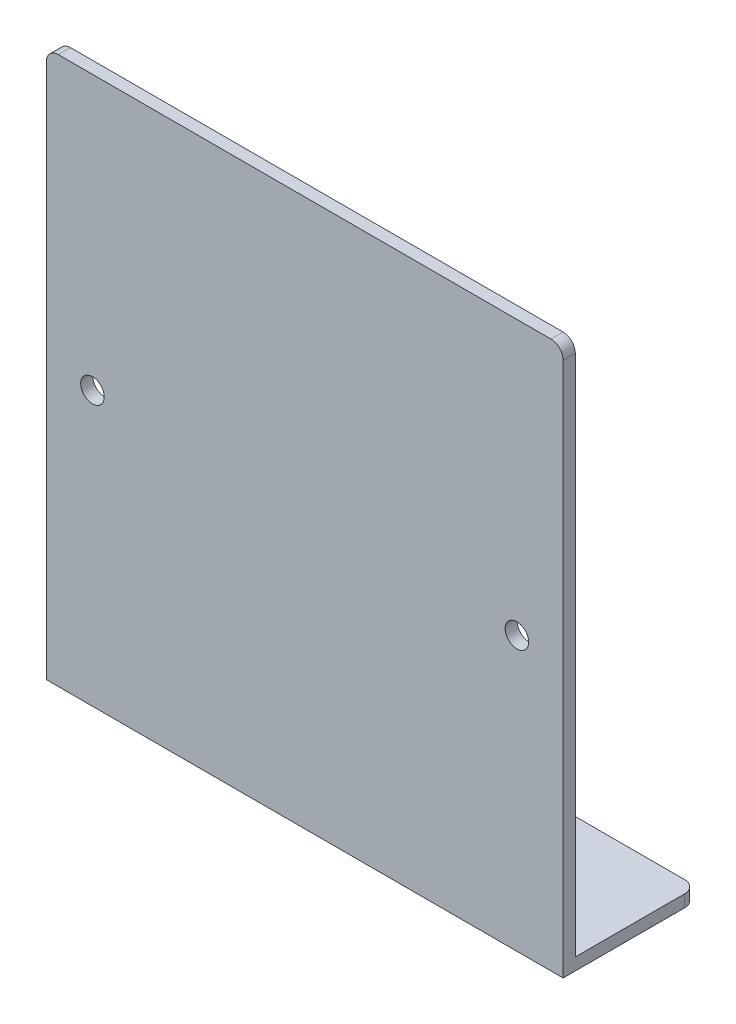
SolidWorks part; units mm, degrees
ref_plane "Front Plane" through (0, 0, 0) normal (0, 0, 1) x (1, 0, 0)
ref_plane "Top Plane" through (0, 0, 0) normal (0, 1, 0) x (1, 0, 0)
ref_plane "Right Plane" through (0, 0, 0) normal (1, 0, 0) x (0, 0, -1)
sketch "Sketch1" plane through (0, 0, 0) normal (0, 1, 0) x (1, 0, 0)
  line L1 (0, 0) -> (107.95, 0)
  line L2 (0, 0) -> (0, 25.4)
  line L3 (0, 25.4) -> (107.95, 25.4)
  line L4 (107.95, 0) -> (107.95, 25.4)
  point P5 (25.4, 12.7)
  point P6 (82.55, 12.7)
  dimension "D1" = 107.95
  dimension "D2" = 25.4
  dimension "D3" = 25.4
  dimension "D4" = 12.7
  dimension "D5" = 25.4
  dimension "D6" = 12.7
extrude "Boss-Extrude2" add sketch "Sketch1" along normal blind 2.54
hole_wizard "#10 (0.1935) Diameter Hole1" positions "Sketch7" profile "Sketch6" hole size "#10" standard "ANSI Inch"
sketch "Sketch7" plane through (0, 2.54, 0) normal (0, 1, 0) x (1, 0, 0)
  line L0 (0, 0) -> (107.95, 0) construction
  line L1 (0, 25.4) -> (0, 0) construction
  line L2 (107.95, 0) -> (107.95, 25.4) construction
  point P0 (25.4, 12.7)
  point P2 (82.55, 12.7)
  dimension "D1" = 12.7
  dimension "D2" = 25.4
  dimension "D3" = 12.7
  dimension "D4" = 25.4
sketch "Sketch6" plane through (25.4, 2.54, -12.7) normal (1, 0, 0) x (0, 0, 1)
  line L0 (0, 0) -> (0, 26.8766)
  line L1 (0, 26.8766) -> (2.4574, 25.4)
  line L2 (2.4574, 25.4) -> (2.4574, 0)
  line L5 (2.4574, 0) -> (0, 0)
  line L10 (0, 26.8766) -> (-2.4575, 25.4) construction
  line L11 (0, -6.35) -> (0, 107.95) construction
  dimension "Hole Dia." = 4.9149
  dimension "Hole Depth" = 25.4
  dimension "Drill Angle" = 118
sketch "Sketch9" plane through (0, 0, 0) normal (0, 0, 1) x (1, 0, 0)
  line L1 (0, 0) -> (107.95, 0)
  line L2 (0, 0) -> (0, 114.3)
  line L3 (0, 114.3) -> (107.95, 114.3)
  line L4 (107.95, 0) -> (107.95, 114.3)
  dimension "D1" = 114.3
  dimension "D2" = 107.95
extrude "Boss-Extrude3" add sketch "Sketch9" along normal blind 2.54
hole_wizard "#10 (0.1935) Diameter Hole2" positions "3DSketch3" profile "Sketch10" hole size "#10" standard "ANSI Inch"
sketch3d "3DSketch3"
  line L0 (107.95, 114.3, 2.54) -> (0, 114.3, 2.54) construction
  line L1 (0, 114.3, 2.54) -> (0, 0, 2.54) construction
  line L2 (107.95, 0, 2.54) -> (107.95, 114.3, 2.54) construction
  point P0 (9.652, 57.15, 2.54)
  point P2 (98.298, 57.15, 2.54)
  dimension "D1" = 57.15
  dimension "D2" = 57.15
  dimension "D3" = 9.652
  dimension "D4" = 9.652
sketch "Sketch10" plane through (9.652, 57.15, 2.54) normal (1, 0, 0) x (0, -1, 0)
  line L0 (0, 0) -> (0, 26.8766)
  line L1 (0, 26.8766) -> (2.4574, 25.4)
  line L2 (2.4574, 25.4) -> (2.4574, 0)
  line L5 (2.4574, 0) -> (0, 0)
  line L10 (0, 26.8766) -> (-2.4574, 25.4) construction
  line L11 (0, -6.35) -> (0, 107.95) construction
  dimension "Hole Dia." = 4.9149
  dimension "Hole Depth" = 25.4
  dimension "Drill Angle" = 118
fillet "Fillet2" radius 2.54 1 edges at (107.95, 114.3, 1.27)
fillet "Fillet3" radius 2.54 1 edges at (0, 114.3, 1.27)
fillet "Fillet4" radius 2.54 1 edges at (107.95, 1.27, -25.4)
fillet "Fillet5" radius 2.54 1 edges at (0, 1.27, -25.4)
equation "\"0.3975n\"=0.39"
